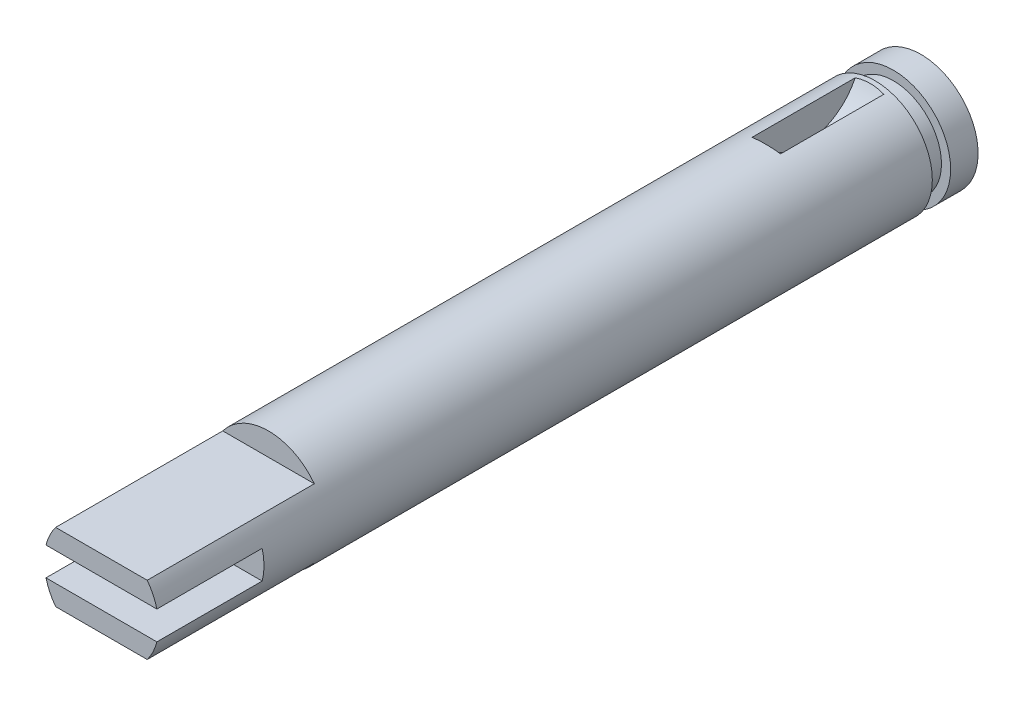
SolidWorks part; units mm, degrees
ref_plane "Front Plane" through (0, 0, 0) normal (0, 0, 1) x (1, 0, 0)
ref_plane "Top Plane" through (0, 0, 0) normal (0, 1, 0) x (1, 0, 0)
ref_plane "Right Plane" through (0, 0, 0) normal (1, 0, 0) x (0, 0, -1)
sketch "Sketch1" plane through (0, 0, 0) normal (0, 0, 1) x (1, 0, 0)
  circle A0 centre (0, 0) radius 3.175
extrude "Extrude1" add sketch "Sketch1" along normal blind 42.926
sketch "Sketch2" plane through (0, 0, 0) normal (0, 0, -1) x (-1, 0, 0)
  line L0 (0, 0) -> (0, 3.175) construction
  circle A0 centre (0, 0) radius 3.175 construction
sketch "Sketch3" plane through (0, 0, 42.926) normal (0, 0, 1) x (1, 0, 0)
  line L0 (0, 0) -> (0, 3.175) construction
  circle A0 centre (0, 0) radius 3.175 construction
ref_plane "Plane1" through (0, 0, 0) normal (1, 0, 0) x (0, 0, -1)
sketch "Sketch4" plane through (0, 0, 0) normal (1, 0, 0) x (0, 0, -1)
  line L0 (0, 3.175) -> (-3.175, 3.175) construction
  line L1 (0, 0) -> (0, 3.175) construction
  line L2 (0, 3.175) -> (-42.926, 3.175) construction
  line L3 (-3.175, 3.175) -> (-3.175, 4.445) construction
  circle A0 centre (-3.175, 4.445) radius 3.175
extrude "Extrude2" cut sketch "Sketch4" against normal blind 0.7937 and the other way blind 0.7937
sketch "Sketch5" plane through (0, 0, 0) normal (0, 0, -1) x (-1, 0, 0)
  circle A0 centre (0, 0) radius 3.175
extrude "Extrude3" add sketch "Sketch5" along normal blind 2.54
sketch "Sketch6" plane through (0, 0, 0) normal (0, 0, 1) x (1, 0, 0)
  circle A0 centre (0, 0) radius 2.667
extrude "Extrude4" cut sketch "Sketch6" against normal blind 1.016 flip side to cut
chamfer "Chamfer1" [suppressed] distance 2.032 angle 60
sketch "Sketch7" plane through (0, 0, 0) normal (1, 0, 0) x (0, 0, -1)
  line L0 (-42.926, 0) -> (-42.926, 0.7874)
  line L1 (-42.926, 0) -> (-42.926, 3.175) construction
  line L2 (-42.926, 0) -> (-37.084, 0) construction
  line L3 (1.016, 0) -> (2.54, 0) construction
  line L4 (-37.084, 0) -> (-37.084, 0.7874)
  line L5 (-37.084, 0.7874) -> (-42.926, 0.7874)
  line L6 (-37.084, 0) -> (-37.084, -0.7874)
  line L7 (-37.084, -0.7874) -> (-42.926, -0.7874)
  line L8 (-42.926, -0.7874) -> (-42.926, 0)
extrude "Extrude5" cut sketch "Sketch7" against normal through all and the other way through all
sketch "Sketch8" plane through (0, 0, 0) normal (1, 0, 0) x (0, 0, -1)
  line L0 (-42.926, 0.7874) -> (-42.926, 1.905) construction
  line L1 (-42.926, 0) -> (-42.926, 3.175) construction
  line L2 (-40.005, 0.7874) -> (-40.005, 3.175) construction
  line L3 (-42.926, 0.7874) -> (-37.084, 0.7874) construction
  line L4 (-6.0849, 3.175) -> (-42.926, 3.175) construction
  line L5 (-42.926, 1.905) -> (-40.005, 1.905)
  line L7 (-40.005, 1.905) -> (-33.655, 1.905)
  line L8 (-33.655, 1.905) -> (-33.655, 3.175)
  line L9 (-33.655, 3.175) -> (-42.926, 3.175)
  line L10 (-42.926, 3.175) -> (-42.926, 1.905)
extrude "Extrude6" cut sketch "Sketch8" against normal through all and the other way through all
sketch "Sketch9" plane through (0, 0, 33.655) normal (0, 0, 1) x (1, 0, 0)
  line L0 (0, 1.905) -> (0, 3.175) construction
  line L1 (-2.54, 1.905) -> (2.54, 1.905) construction
  arc A0 (2.54, 1.905) -> (-2.54, 1.905) centre (0, 0) ccw construction
mirror "Mirror1" about plane through (0, 0, 0) normal (0, 1, 0) of "Extrude6"
sketch "Sketch10" plane through (0.7937, 0, 0) normal (-1, 0, 0) x (0, 0, 1)
  arc A0 (0.3112, 3.0742) -> (6.0388, 3.0742) centre (3.175, 4.445) ccw construction
  point P0 (3.175, 1.27)
